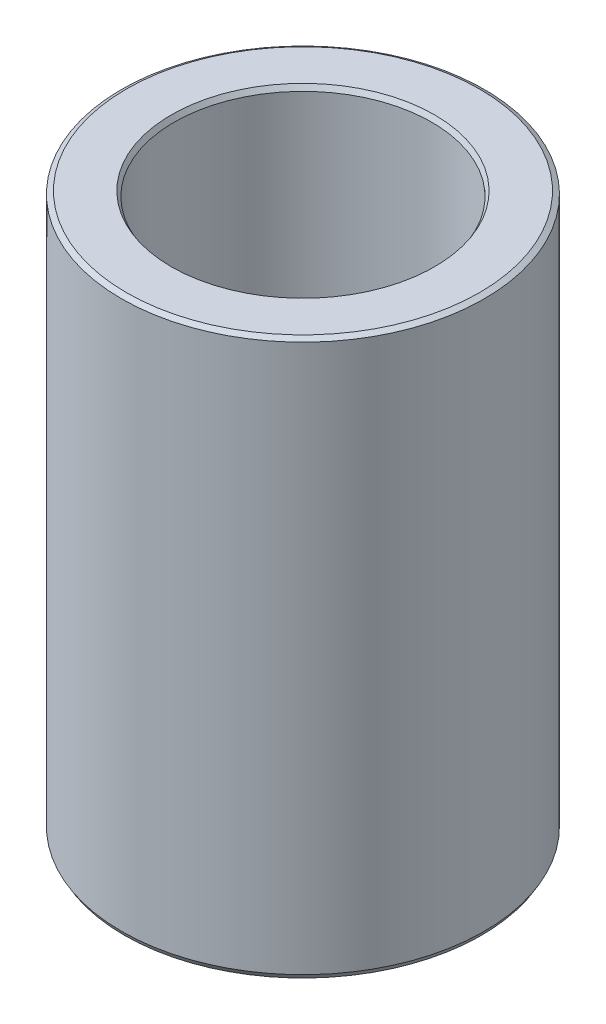
SolidWorks part; units mm, degrees
ref_plane "Front Plane" through (0, 0, 0) normal (0, 0, 1) x (1, 0, 0)
ref_plane "Top Plane" through (0, 0, 0) normal (0, 1, 0) x (1, 0, 0)
ref_plane "Right Plane" through (0, 0, 0) normal (1, 0, 0) x (0, 0, -1)
sketch "Sketch1" plane through (0, 0, 0) normal (0, 1, 0) x (1, 0, 0)
  circle A0 centre (0, 0) radius 22.5
  dimension "SLEEVE_OD" = 45
extrude "Boss-Extrude1" add sketch "Sketch1" along normal blind 68.912
sketch "Sketch2" plane through (0, 0, 0) normal (0, 1, 0) x (1, 0, 0)
  circle A0 centre (0, 0) radius 15.9757
  dimension "BORE_D" = 31.9513
extrude "Cut-Extrude1" cut sketch "Sketch2" along normal through all
chamfer "Chamfer1" distance 0.3529 angle 60 4 edges at (0, 68.912, 15.9757) (0, 0, 15.9757) (0, 0, 22.5) (0, 68.912, 22.5) first distance on face at (0, 68.912, 15.9757) first distance on face at (0, 0, 15.9757) first distance on face at (0, 68.912, 22.5)
